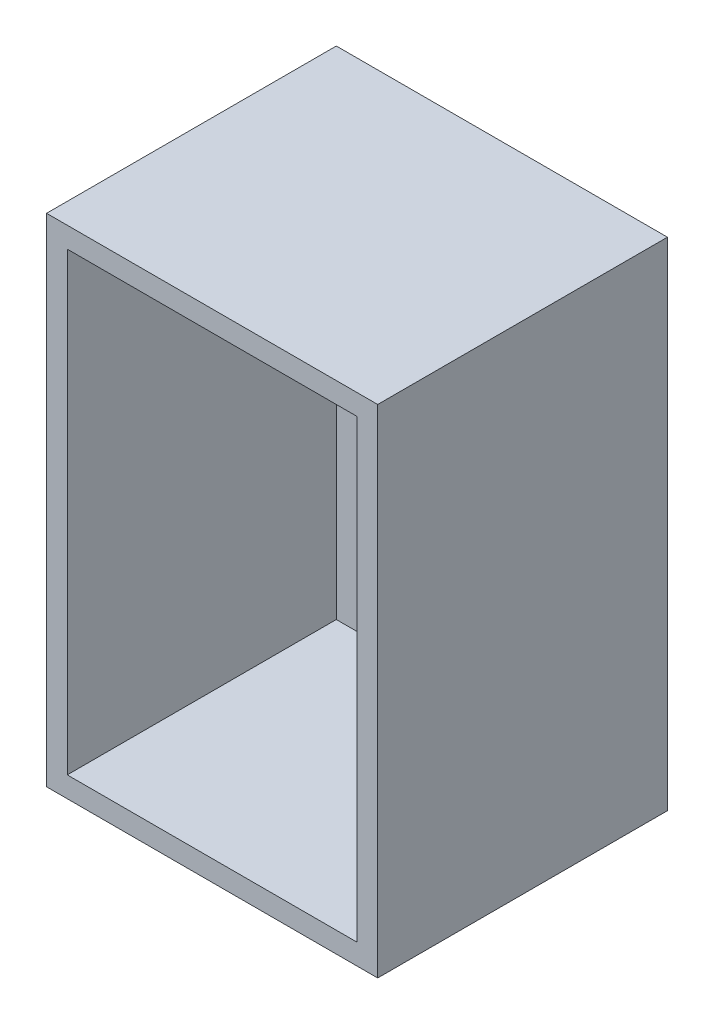
SolidWorks part; units mm, degrees
ref_plane "Front Plane" through (0, 0, 0) normal (0, 0, 1) x (1, 0, 0)
ref_plane "Top Plane" through (0, 0, 0) normal (0, 1, 0) x (1, 0, 0)
ref_plane "Right Plane" through (0, 0, 0) normal (1, 0, 0) x (0, 0, -1)
sketch "Sketch4" plane through (0, 0, 0) normal (0, 0, 1) x (1, 0, 0)
  line L1 (-25.2849, 20.5607) -> (14.7151, 20.5607)
  line L2 (-25.2849, 20.5607) -> (-25.2849, -39.4393)
  line L3 (-25.2849, -39.4393) -> (14.7151, -39.4393)
  line L4 (14.7151, 20.5607) -> (14.7151, -39.4393)
  dimension "D1" = 40
  dimension "D2" = 60
extrude "Boss-Extrude2" add sketch "Sketch4" along normal blind 35
sketch "Sketch5" plane through (0, 0, 35) normal (0, 0, 1) x (1, 0, 0)
  line L0 (-22.7849, 18.0607) -> (-22.7849, -36.9393)
  line L1 (-25.2849, 20.5607) -> (14.7151, 20.5607)
  line L2 (-25.2849, 20.5607) -> (-25.2849, -39.4393)
  line L3 (-25.2849, -39.4393) -> (14.7151, -39.4393)
  line L4 (14.7151, 20.5607) -> (14.7151, -39.4393)
  line L5 (-22.7849, -36.9393) -> (12.2151, -36.9393)
  line L6 (12.2151, 18.0607) -> (12.2151, -36.9393)
  line L7 (-22.7849, 18.0607) -> (12.2151, 18.0607)
  dimension "D1" = 2.5
extrude "Cut-Extrude1" cut sketch "Sketch5" against normal blind 32.5 flip side to cut
